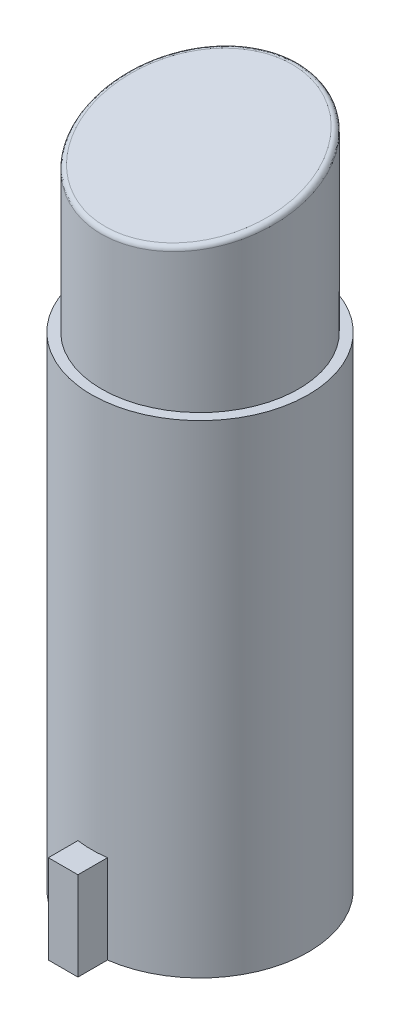
SolidWorks part; units mm, degrees
ref_plane "正面" through (0, 0, 0) normal (0, 0, 1) x (1, 0, 0)
ref_plane "平面" through (0, 0, 0) normal (0, 1, 0) x (1, 0, 0)
ref_plane "右側面" through (0, 0, 0) normal (1, 0, 0) x (0, 0, -1)
sketch "ｽｹｯﾁ1" plane through (0, 0, 0) normal (0, 1, 0) x (1, 0, 0)
  circle A0 centre (0, 0) radius 11
  dimension "D1" = 22
extrude "ﾎﾞｽ - 押し出し1" add sketch "ｽｹｯﾁ1" along normal blind 68
sketch "ｽｹｯﾁ2" plane through (0, 68, 0) normal (0, 1, 0) x (1, 0, 0)
  circle A0 centre (0, 0) radius 10
  circle A1 centre (0, 0) radius 11
  circle A2 centre (0, 0) radius 11
  dimension "D2" = 1
  dimension "D1" = 0
extrude "ｶｯﾄ - 押し出し1" cut sketch "ｽｹｯﾁ2" against normal blind 19
sketch "ｽｹｯﾁ3" plane through (0, 0, 0) normal (1, 0, 0) x (0, 0, -1)
  line L0 (10, 68) -> (-10, 68) construction
  line L1 (10, 68) -> (-10, 68)
  line L2 (-10, 68) -> (-10, 49) construction
  line L3 (-10, 68) -> (-10, 49)
  line L4 (10, 49) -> (10, 68) construction
  line L5 (10, 49) -> (10, 68)
  line L6 (-10, 63) -> (10, 68)
  dimension "D1" = 5
extrude "ｶｯﾄ - 押し出し2" cut sketch "ｽｹｯﾁ3" against normal through all both and the other way through all contours L3 L6 L1 region at (0, 66.3333, 3.3333)
fillet "ﾌｨﾚｯﾄ1" radius 0.5 1 edges at (0, 68, -10)
shell "ｼｪﾙ2" thickness 1 removed face at (0, 0, 11)
sketch "ｽｹｯﾁ5" plane through (0, 0, 0) normal (0, -1, 0) x (1, 0, 0)
  line L1 (-1.5, 13.8972) -> (1.5, 13.8972)
  line L2 (-1.5, 13.8972) -> (-1.5, 10.8972)
  line L3 (-1.5, 10.8972) -> (1.5, 10.8972)
  line L4 (1.5, 13.8972) -> (1.5, 10.8972)
  circle A0 centre (0, 0) radius 11 construction
  point P6 (1.4248, 10.8866)
  dimension "D1" = 3
  dimension "D2" = 3
extrude "ﾎﾞｽ - 押し出し2" add sketch "ｽｹｯﾁ5" against normal blind 9
